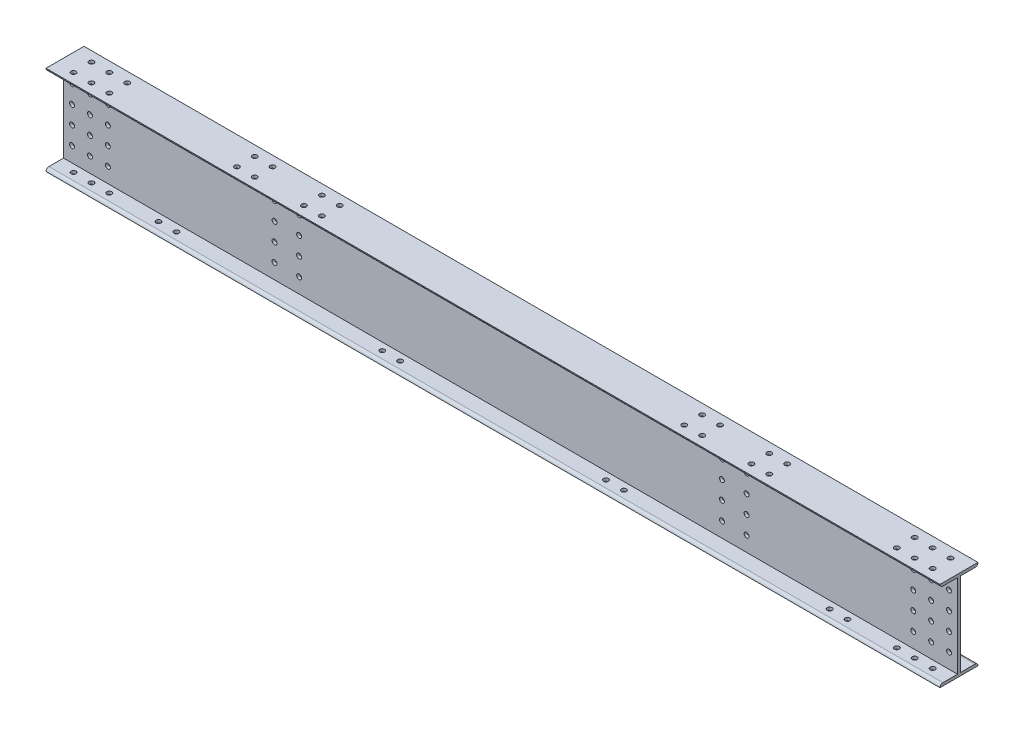
SolidWorks part; units mm, degrees
ref_plane "前视基准面" through (0, 0, 0) normal (0, 0, 1) x (1, 0, 0)
ref_plane "上视基准面" through (0, 0, 0) normal (0, 1, 0) x (1, 0, 0)
ref_plane "右视基准面" through (0, 0, 0) normal (1, 0, 0) x (0, 0, -1)
sketch "草图1" plane through (0, 0, 0) normal (0, 0, 1) x (1, 0, 0)
  line L1 (0, 400) -> (3996, 400)
  line L2 (0, 400) -> (0, 0)
  line L3 (0, 0) -> (3996, 0)
  line L4 (3996, 400) -> (3996, 0)
  dimension "D1" = 3996
  dimension "D2" = 400
extrude "拉伸1" add sketch "草图1" along normal blind 170
sketch "草图2" plane through (0, 0, 170) normal (0, 0, 1) x (1, 0, 0)
  line L0 (0, 400) -> (0, 0) construction
  line L1 (0, 0) -> (3996, 0) construction
  circle A0 centre (38, 80) radius 11
  dimension "D1" = 38
  dimension "D2" = 80
extrude "切除-拉伸1" cut sketch "草图2" against normal through all
pattern_linear "阵列(线性)1" count 4 spacing 80 along (0, 1, 0) of "切除-拉伸1"
pattern_linear "阵列(线性)8" count 2 spacing 80 along (1, 0, 0) of "切除-拉伸1", "阵列(线性)1"
pattern_linear "阵列(线性)9" count 2 spacing 160 along (1, 0, 0) of "切除-拉伸1", "阵列(线性)1"
pattern_linear "阵列(线性)11" count 2 spacing 3760 along (1, 0, 0) of "切除-拉伸1", "阵列(线性)1", "阵列(线性)8", "阵列(线性)9"
pattern_linear "阵列(线性)12" count 2 spacing 905 along (1, 0, 0) of "切除-拉伸1", "阵列(线性)1"
pattern_linear "阵列(线性)13" count 2 spacing 1015 along (1, 0, 0) of "切除-拉伸1", "阵列(线性)1"
pattern_linear "阵列(线性)15" count 2 spacing 3015 along (1, 0, 0) of "切除-拉伸1", "阵列(线性)1"
pattern_linear "阵列(线性)17" count 2 spacing 2905 along (1, 0, 0) of "切除-拉伸1", "阵列(线性)1"
sketch "草图3" plane through (0, 400, 0) normal (0, 1, 0) x (1, 0, 0)
  line L1 (0, -170) -> (0, 0) construction
  circle A0 centre (78, -125) radius 11
  point P0 (0, -85)
  dimension "D1" = 40
  dimension "D2" = 78
extrude "切除-拉伸2" cut sketch "草图3" against normal blind 120
pattern_linear "阵列(线性)18" count 2 spacing 80 along (0, 0, -1) of "切除-拉伸2"
pattern_linear "阵列(线性)19" count 3 spacing 80 along (1, 0, 0) of "切除-拉伸2", "阵列(线性)18"
pattern_linear "阵列(线性)20" count 2 spacing 3680 along (1, 0, 0) of "切除-拉伸2", "阵列(线性)18", "阵列(线性)19"
pattern_linear "阵列(线性)21" count 2 spacing 730 along (1, 0, 0) of "切除-拉伸2", "阵列(线性)18"
pattern_linear "阵列(线性)22" count 2 spacing 810 along (1, 0, 0) of "切除-拉伸2", "阵列(线性)18"
pattern_linear "阵列(线性)24" count 2 spacing 1030 along (1, 0, 0) of "切除-拉伸2", "阵列(线性)18"
pattern_linear "阵列(线性)25" count 2 spacing 1110 along (1, 0, 0) of "切除-拉伸2", "阵列(线性)18"
pattern_linear "阵列(线性)26" count 2 spacing 3110 along (1, 0, 0) of "切除-拉伸2", "阵列(线性)18"
pattern_linear "阵列(线性)27" count 2 spacing 3030 along (1, 0, 0) of "切除-拉伸2", "阵列(线性)18"
pattern_linear "阵列(线性)28" count 2 spacing 2810 along (1, 0, 0) of "切除-拉伸2", "阵列(线性)18"
pattern_linear "阵列(线性)29" count 2 spacing 2730 along (1, 0, 0) of "切除-拉伸2", "阵列(线性)18"
sketch "草图4" plane through (0, 0, 0) normal (0, -1, 0) x (1, 0, 0)
  line L0 (0, 170) -> (0, 0) construction
  line L2 (0, 170) -> (0, 0) construction
  circle A0 centre (78, 45) radius 11
  point P2 (0, 85)
  dimension "D1" = 40
  dimension "D2" = 78
extrude "切除-拉伸3" cut sketch "草图4" against normal blind 120
pattern_linear "阵列(线性)39" count 2 spacing 80 along (0, 0, 1) of "切除-拉伸3"
pattern_linear "阵列(线性)40" count 2 spacing 80 along (1, 0, 0) of "切除-拉伸3", "阵列(线性)39"
pattern_linear "阵列(线性)41" count 2 spacing 160 along (1, 0, 0) of "切除-拉伸3", "阵列(线性)39"
pattern_linear "阵列(线性)43" count 2 spacing 1380 along (1, 0, 0) of "切除-拉伸3", "阵列(线性)39", "阵列(线性)40"
pattern_linear "阵列(线性)44" count 2 spacing 380 along (1, 0, 0) of "切除-拉伸3", "阵列(线性)39", "阵列(线性)40"
pattern_linear "阵列(线性)46" count 2 spacing 2380 along (1, 0, 0) of "切除-拉伸3", "阵列(线性)39", "阵列(线性)40"
pattern_linear "阵列(线性)47" count 2 spacing 3380 along (1, 0, 0) of "切除-拉伸3", "阵列(线性)39", "阵列(线性)40"
pattern_linear "阵列(线性)48" count 2 spacing 3680 along (1, 0, 0) of "切除-拉伸3", "阵列(线性)39", "阵列(线性)40", "阵列(线性)41"
sketch "草图6" plane through (0, 0, 0) normal (-1, 0, 0) x (0, 0, 1)
  line L0 (170, 400) -> (0, 400) construction
  line L1 (170, 0) -> (0, 0) construction
  line L2 (0, 400) -> (0, 0) construction
  line L3 (0, 387) -> (78.5, 387)
  line L4 (0, 387) -> (0, 13)
  line L5 (0, 13) -> (78.5, 13)
  line L6 (78.5, 387) -> (78.5, 13)
  line L7 (170, 400) -> (170, 0) construction
  line L8 (170, 387) -> (91.5, 387)
  line L9 (170, 387) -> (170, 13)
  line L10 (170, 13) -> (91.5, 13)
  line L11 (91.5, 387) -> (91.5, 13)
  line L12 (170, 400) -> (0, 400) construction
  point P1 (85, 400)
  dimension "D1" = 6.5
  dimension "D2" = 13
  dimension "D3" = 13
extrude "切除-拉伸4" cut sketch "草图6" against normal through all
fillet "圆角1" radius 13 1 edges at (1998, 13, 170)
fillet "圆角2" radius 13 1 edges at (1998, 13, 0)
fillet "圆角3" radius 13 1 edges at (1998, 387, 170)
fillet "圆角4" radius 13 1 edges at (1998, 387, 0)
